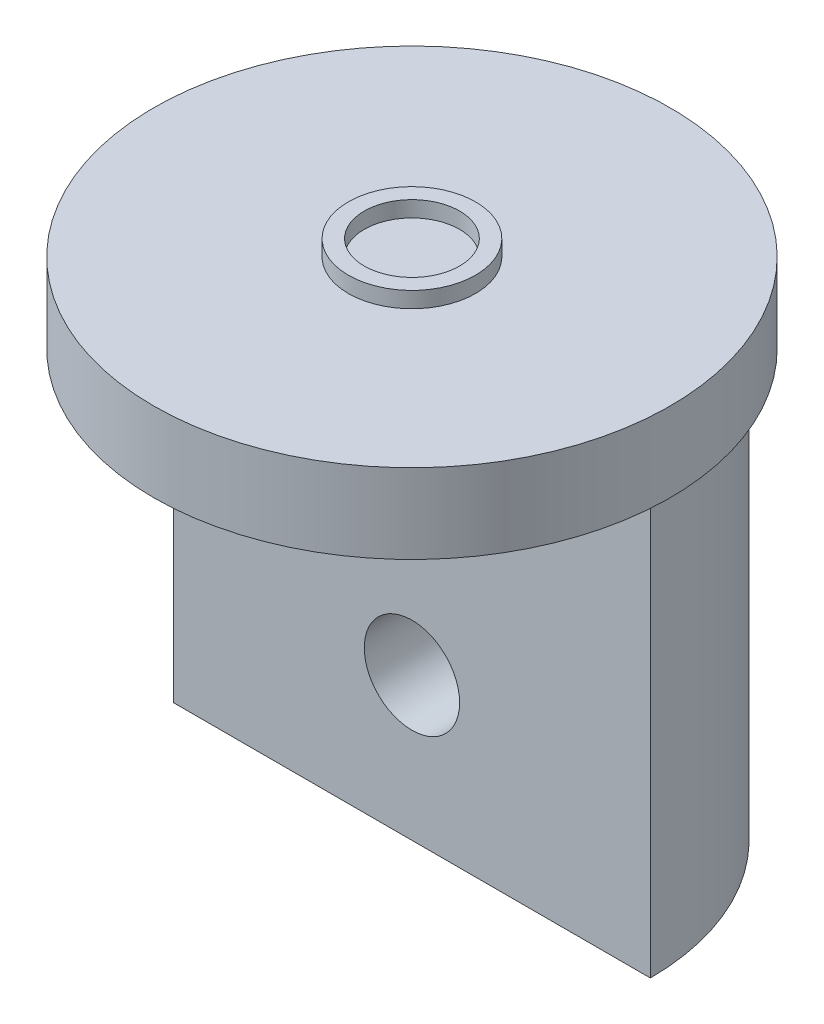
SolidWorks part; units mm, degrees
ref_plane "Front Plane" through (0, 0, 0) normal (0, 0, 1) x (1, 0, 0)
ref_plane "Top Plane" through (0, 0, 0) normal (0, 1, 0) x (1, 0, 0)
ref_plane "Right Plane" through (0, 0, 0) normal (1, 0, 0) x (0, 0, -1)
sketch "Sketch1" plane through (0, 0, 0) normal (0, 1, 0) x (1, 0, 0)
  line L0 (30, 0) -> (-30, 0) construction
  circle A0 centre (0, 0) radius 32.5
  circle A1 centre (0, 0) radius 30
  dimension "D1" = 65
extrude "Boss-Extrude3" add sketch "Sketch1" against normal blind 10
extrude "Boss-Extrude4" add sketch "Sketch1<3>" against normal blind 63.5872 contours L0 A1 region at (0, 0, -12.7324)
sketch "Sketch1<3>" plane through (0, 0, 0) normal (0, 1, 0) x (1, 0, 0) same geometry as "Sketch1"
extrude "Boss-Extrude5" add sketch "Sketch1<4>" against normal blind 10 contours A1 L0 region at (0, 0, 12.7324)
sketch "Sketch1<4>" plane through (0, 0, 0) normal (0, 1, 0) x (1, 0, 0) same geometry as "Sketch1"
sketch "Sketch2" plane through (0, 0, 0) normal (0, 0, 1) x (1, 0, 0)
  line L0 (0, -63.5872) -> (0, -45.5872) construction
  line L1 (30, -63.5872) -> (-30, -63.5872) construction
  circle A0 centre (0, -45.5872) radius 6
  dimension "D2" = 12
  dimension "D1" = 18
extrude "Cut-Extrude1" cut sketch "Sketch2" against normal blind 45
sketch "Sketch3" plane through (0, 0, 0) normal (0, 1, 0) x (1, 0, 0)
  circle A0 centre (0, 0) radius 6
  circle A1 centre (0, 0) radius 8
  dimension "D1" = 16
  dimension "D2" = 12
extrude "Boss-Extrude6" add sketch "Sketch3" along normal blind 2
